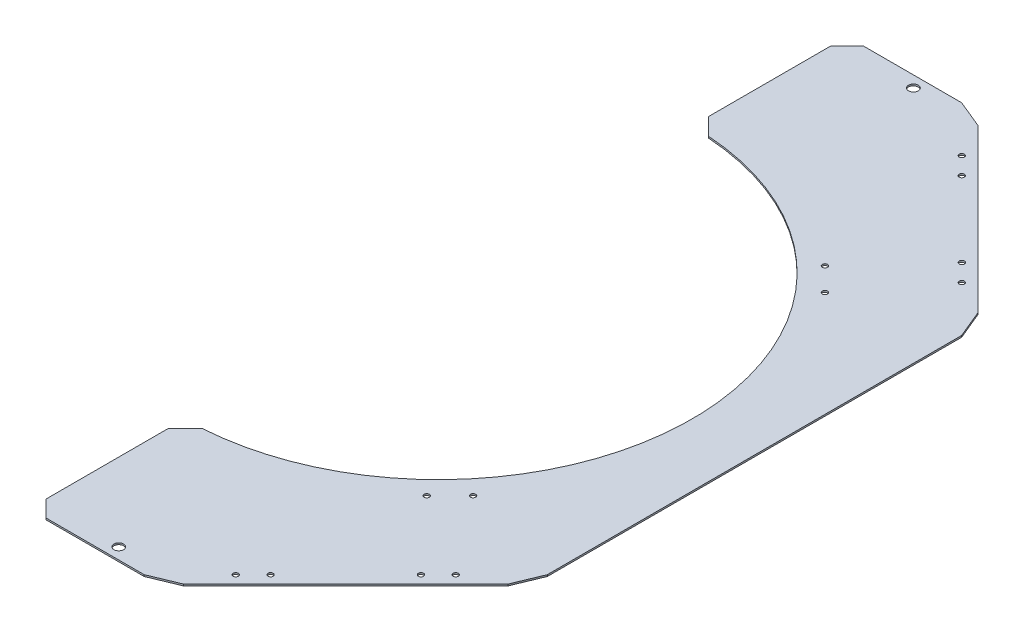
SolidWorks part; units mm, degrees
ref_plane "前视基准面" through (0, 0, 0) normal (0, 0, 1) x (1, 0, 0)
ref_plane "上视基准面" through (0, 0, 0) normal (0, 1, 0) x (1, 0, 0)
ref_plane "右视基准面" through (0, 0, 0) normal (1, 0, 0) x (0, 0, -1)
sketch "草图1" plane through (0, 0, 0) normal (0, 1, 0) x (1, 0, 0)
  line L0 (0, 0) -> (0, 249.7056)
  line L1 (0, 249.7056) -> (80, 249.7056)
  line L2 (80, 249.7056) -> (249.7056, 80)
  line L3 (249.7056, 80) -> (249.7056, 0)
  line L4 (249.7056, 0) -> (249.7056, -80)
  line L5 (249.7056, -80) -> (80, -249.7056)
  line L6 (80, -249.7056) -> (0, -249.7056)
  line L7 (0, -249.7056) -> (0, 0)
  line L8 (0, 0) -> (249.7056, 0) construction
  line L9 (0, 0) -> (164.8528, 164.8528) construction
  line L10 (80, -249.7056) -> (80, 249.7056) construction
  circle A4 centre (0, 0) radius 155
  dimension "D5" = 80
  dimension "D7" = 310
  dimension "D3" = 80
  dimension "D6" = 240
extrude "凸台-拉伸1" add sketch "草图1" along normal blind 1
sketch "草图4" plane through (0, 1, 0) normal (0, 1, 0) x (1, 0, 0)
  line L0 (80, 249.7056) -> (249.7056, 80) construction
  line L1 (193.1371, 136.5685) -> (249.7056, 136.5685)
  line L2 (193.1371, 136.5685) -> (193.1371, -136.5685)
  line L3 (193.1371, -136.5685) -> (249.7056, -136.5685)
  line L4 (249.7056, 136.5685) -> (249.7056, -136.5685)
  line L5 (249.7056, -80) -> (80, -249.7056) construction
  line L6 (249.7056, 80) -> (249.7056, -80) construction
  line L7 (193.1371, 136.5685) -> (249.7056, 80) construction
  dimension "D1" = 80
extrude "切除-拉伸3" cut sketch "草图4" against normal through all
chamfer "倒角1" distance 10 8 edges at (193.1371, 0.5, 136.5685) (80, 0.5, 249.7056) (0, 0.5, 155) (0, 0.5, -155) (0, 0.5, -249.7056) (80, 0.5, -249.7056) (193.1371, 0.5, -136.5685) (0, 0.5, 249.7056)
sketch "草图5" plane through (0, 1, 0) normal (0, 1, 0) x (1, 0, 0)
  line L0 (0, 0) -> (193.1371, 0) construction
  line L1 (193.1371, 126.5685) -> (193.1371, -126.5685) construction
  line L2 (108.6378, -211.1683) -> (98.0312, -221.7749) construction
  line L3 (103.3345, -216.4716) -> (108.2843, -221.4214) construction
  line L5 (186.066, -143.6396) -> (87.0711, -242.6346) construction
  line L6 (136.5685, -193.1371) -> (115.3553, -171.9239) construction
  line L7 (159.9031, -159.9031) -> (164.8528, -164.8528) construction
  line L8 (154.5998, -165.2064) -> (165.2064, -154.5998) construction
  line L9 (154.5998, 165.2064) -> (165.2064, 154.5998) construction
  line L10 (159.9031, 159.9031) -> (164.8528, 164.8528) construction
  line L11 (136.5685, 193.1371) -> (115.3553, 171.9239) construction
  line L12 (103.3345, 216.4716) -> (108.2843, 221.4214) construction
  line L13 (108.6378, 211.1683) -> (98.0312, 221.7749) construction
  circle A0 centre (98.0312, -221.7749) radius 1.6
  circle A1 centre (108.6378, -211.1683) radius 1.6
  circle A2 centre (154.5998, -165.2064) radius 1.6
  circle A3 centre (165.2064, -154.5998) radius 1.6
  circle A4 centre (165.2064, 154.5998) radius 1.6
  circle A5 centre (154.5998, 165.2064) radius 1.6
  circle A6 centre (108.6378, 211.1683) radius 1.6
  circle A7 centre (98.0312, 221.7749) radius 1.6
  dimension "D3" = 3.2
  dimension "D1" = 7
  dimension "D2" = 15
  dimension "D4" = 30
  dimension "D5" = 40
extrude "切除-拉伸4" cut sketch "草图5" against normal blind 10
sketch "草图6" plane through (0, 1, 0) normal (0, 1, 0) x (1, 0, 0)
  line L0 (47.5, -242.75) -> (47.5, 242.75) construction
  line L1 (47.5, 0) -> (0, 0) construction
  circle A0 centre (47.5, 242.75) radius 3
  circle A1 centre (47.5, -242.75) radius 3
  dimension "D3" = 6
  dimension "D1" = 47.5
  dimension "D2" = 485.5
extrude "切除-拉伸5" cut sketch "草图6" against normal blind 10
sketch "草图7" plane through (0, 1, 0) normal (0, 1, 0) x (1, 0, 0)
  line L0 (137.8921, 109.6079) -> (109.6079, 137.8921) construction
  line L1 (0, 0) -> (123.75, 123.75) construction
  line L4 (106.0723, 134.3566) -> (134.3566, 106.0723) construction
  line L5 (134.3566, 106.0723) -> (130.114, 101.8297) construction
  line L6 (130.114, 101.8297) -> (101.8297, 130.114) construction
  line L7 (101.8297, 130.114) -> (106.0723, 134.3566) construction
  line L9 (103.951, 132.2353) -> (132.2353, 103.951) construction
  line L10 (0, 0) -> (193.1371, 0) construction
  line L11 (193.1371, 126.5685) -> (193.1371, -126.5685) construction
  circle A0 centre (114.5576, 121.6287) radius 1.6
  circle A1 centre (128.6997, 107.4865) radius 1.6
  circle A2 centre (128.6997, -107.4865) radius 1.6
  circle A3 centre (114.5576, -121.6287) radius 1.6
  point P20 (120.2145, 120.2145)
  dimension "D8" = 3.2
  dimension "D1" = 45
  dimension "D2" = 175.0089
  dimension "D3" = 6
  dimension "D4" = 40
  dimension "D5" = 5
  dimension "D6" = 20
  dimension "D7" = 5
  dimension "D9" = 40
extrude "切除-拉伸6" cut sketch "草图7" against normal blind 4
